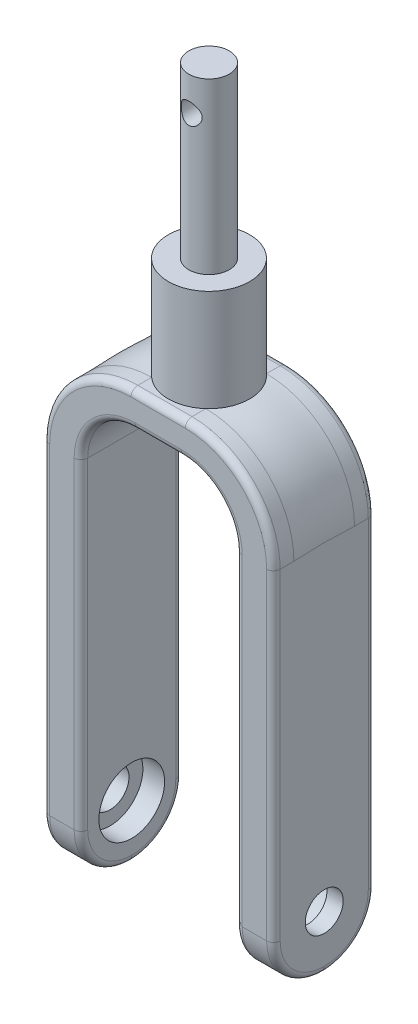
SolidWorks part; units mm, degrees
ref_plane "前视基准面" through (0, 0, 0) normal (0, 0, 1) x (1, 0, 0)
ref_plane "上视基准面" through (0, 0, 0) normal (0, 1, 0) x (1, 0, 0)
ref_plane "右视基准面" through (0, 0, 0) normal (1, 0, 0) x (0, 0, -1)
sketch "草图1" plane through (0, 0, 0) normal (0, 1, 0) x (1, 0, 0)
  line L1 (17, 7.5) -> (-17, 7.5)
  line L2 (17, 7.5) -> (17, -7.5)
  line L3 (17, -7.5) -> (-17, -7.5)
  line L4 (-17, 7.5) -> (-17, -7.5)
  line L5 (17, 7.5) -> (-17, -7.5) construction
  line L6 (17, -7.5) -> (-17, 7.5) construction
  point P0 (0, 0)
extrude "凸台-拉伸1" add sketch "草图1" against normal blind 68
sketch "草图2" plane through (0, 0, 0) normal (0, 1, 0) x (1, 0, 0)
  circle A0 centre (0, 0) radius 6
extrude "凸台-拉伸2" add sketch "草图2" along normal blind 15
sketch "草图7" plane through (0, 15, 0) normal (0, 1, 0) x (1, 0, 0)
  circle A0 centre (0, 0) radius 2.98
extrude "凸台-拉伸3" add sketch "草图7" along normal blind 25
sketch "草图8" plane through (0, 0, 0) normal (0, 0, 1) x (1, 0, 0)
  line L0 (0, 15) -> (0, 35) construction
  line L1 (6, 15) -> (-6, 15) construction
  circle A1 centre (0, 35) radius 1.55
extrude "切除-拉伸5" cut sketch "草图8" against normal through all both and the other way through all
sketch "草图3" plane through (0, 0, 7.5) normal (0, 0, 1) x (1, 0, 0)
  line L0 (-17, -68) -> (17, -68) construction
  line L1 (-11.4, -68) -> (11.4, -68)
  line L2 (-11.4, -68) -> (-11.4, -5)
  line L3 (-11.4, -5) -> (11.4, -5)
  line L4 (11.4, -68) -> (11.4, -5)
extrude "切除-拉伸1" cut sketch "草图3" against normal through all
fillet "圆角1" radius 8 2 edges at (11.4, -5, 0) (-11.4, -5, 0)
fillet "圆角5" radius 13 2 edges at (17, 0, 0) (-17, 0, 0)
fillet "圆角3" radius 7.5 4 edges at (14.2, -68, -7.5) (14.2, -68, 7.5) (-14.2, -68, -7.5) (-14.2, -68, 7.5)
fillet "圆角2" radius 1 28 edges at (-17, -36.75, -7.5) (0, 0, -7.5) (17, -36.75, -7.5) (17, -36.75, 7.5) (0, 0, 7.5) (-17, -36.75, 7.5) (-9.0569, -7.3431, 7.5) (0, -5, 7.5) (9.0569, -7.3431, 7.5) (11.4, -36.75, 7.5) (11.4, -36.75, -7.5) (9.0569, -7.3431, -7.5) (0, -5, -7.5) (-9.0569, -7.3431, -7.5) (-11.4, -36.75, -7.5) (-11.4, -36.75, 7.5) (11.4, -65.8033, 5.3033) (11.4, -65.8033, -5.3033) (-11.4, -65.8033, -5.3033) (-11.4, -65.8033, 5.3033) (-17, -65.8033, 5.3033) (-17, -65.8033, -5.3033) (17, -65.8033, -5.3033) (17, -65.8033, 5.3033) (-13.1924, -3.8076, -7.5) (13.1924, -3.8076, -7.5) (13.1924, -3.8076, 7.5) (-13.1924, -3.8076, 7.5)
sketch "草图4" plane through (17, 0, 0) normal (1, 0, 0) x (0, 0, -1)
  circle A0 centre (0, -60) radius 2.8
extrude "切除-拉伸2" cut sketch "草图4" against normal through all
sketch "草图6" plane through (11.4, 0, 0) normal (1, 0, 0) x (0, 0, -1)
  circle A0 centre (0, -60) radius 4.85
extrude "切除-拉伸4" cut sketch "草图6" along normal blind 3.2
mirror "镜向1" about plane through (0, 0, 0) normal (1, 0, 0) of "切除-拉伸4"
